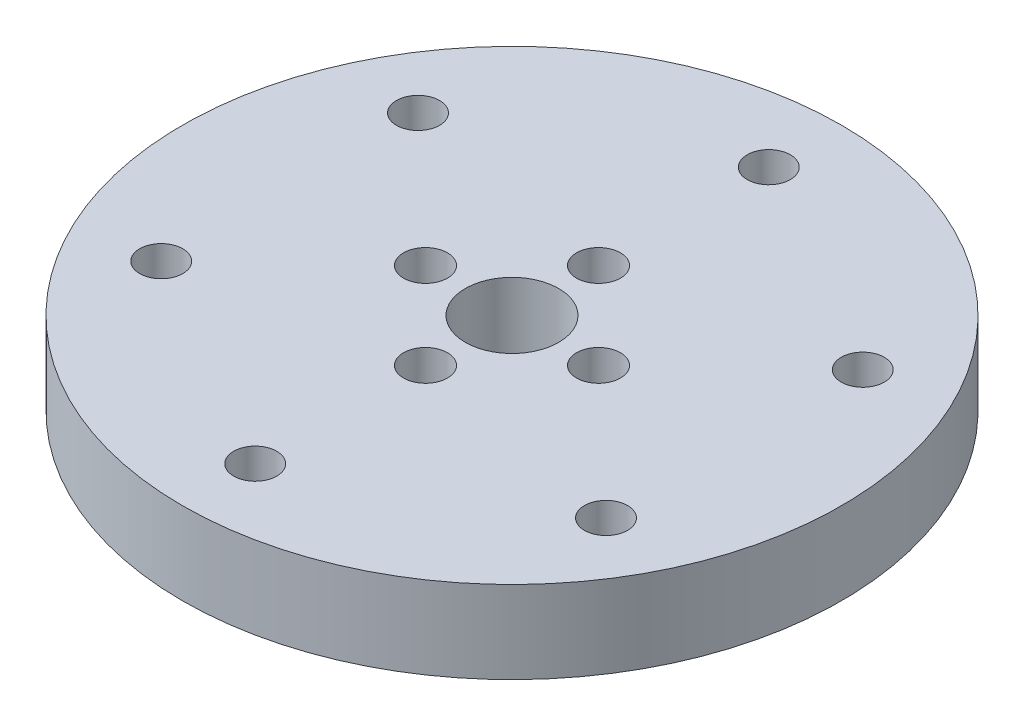
SolidWorks part; units mm, degrees
ref_plane "Front Plane" through (0, 0, 0) normal (0, 0, 1) x (1, 0, 0)
ref_plane "Top Plane" through (0, 0, 0) normal (0, 1, 0) x (1, 0, 0)
ref_plane "Right Plane" through (0, 0, 0) normal (1, 0, 0) x (0, 0, -1)
sketch "Sketch1" plane through (0, 0, 0) normal (0, 1, 0) x (1, 0, 0)
  circle A0 centre (0, 0) radius 30.48
  dimension "D1" = 60.96
extrude "Boss-Extrude1" add sketch "Sketch1" along normal blind 7.62 contours A0
sketch "Sketch2" plane through (0, 7.62, 0) normal (0, 1, 0) x (1, 0, 0)
  line L0 (0, 0) -> (0, -23.749)
  circle A0 centre (0, 0) radius 23.749
  circle A1 centre (0, -23.749) radius 1.9939
  dimension "D1" = 47.498
  dimension "D2" = 3.9878
extrude "Cut-Extrude1" cut sketch "Sketch2" against normal through all contours A1
pattern_circular "CirPattern1" count 6 over 360 about axis through (0, 7.62, 0) along (0, -1, 0) of "Cut-Extrude1"
sketch "Sketch3" plane through (0, 7.62, 0) normal (0, 1, 0) x (1, 0, 0)
  circle A0 centre (0, 0) radius 4.318
  circle A2 centre (0, -8.001) radius 2.032
  dimension "D1" = 8.636
  dimension "D3" = 4.064
extrude "Cut-Extrude2" cut sketch "Sketch3" against normal through all contours A0 | A2
pattern_circular "CirPattern2" count 4 over 360 about axis through (0, 7.62, 0) along (0, -1, 0) of "Cut-Extrude2"
